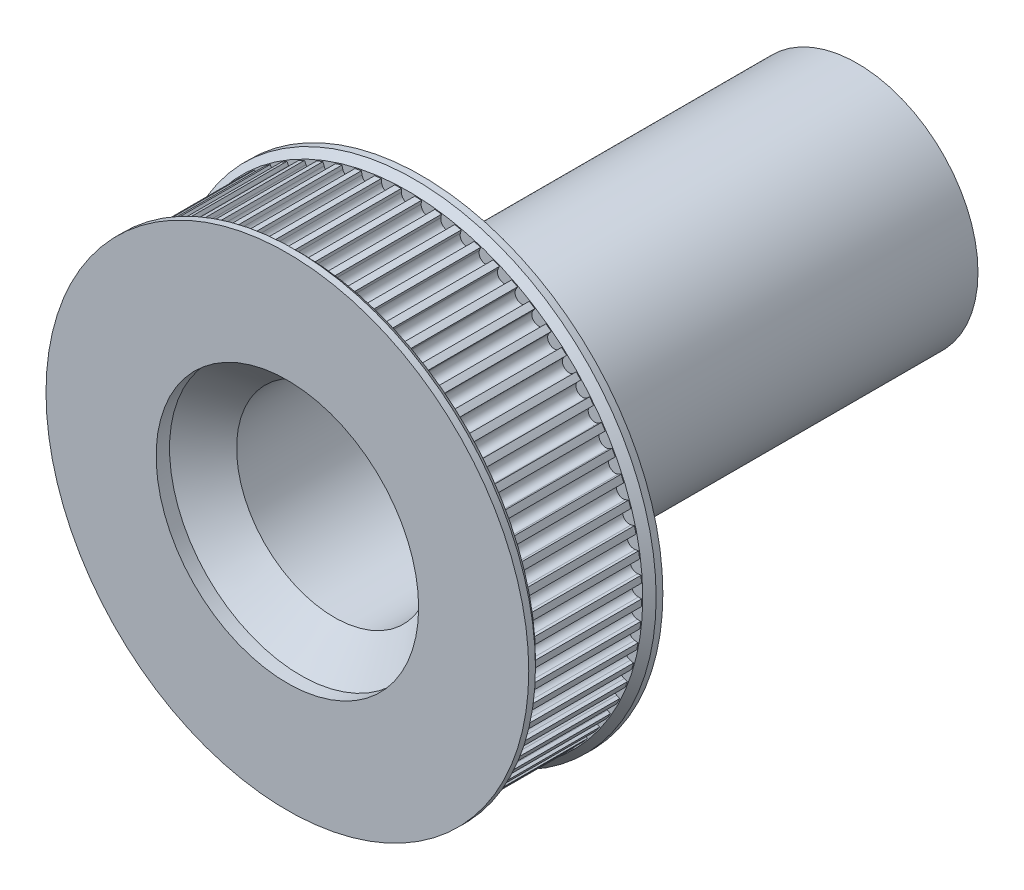
SolidWorks part; units mm, degrees
material "PA Type 6"
ref_plane "Front Plane" through (0, 0, 0) normal (0, 0, 1) x (1, 0, 0)
ref_plane "Top Plane" through (0, 0, 0) normal (0, 1, 0) x (1, 0, 0)
ref_plane "Right Plane" through (0, 0, 0) normal (1, 0, 0) x (0, 0, -1)
sketch "Sketch1" plane through (0, 0, 0) normal (0, 0, 1) x (1, 0, 0)
  circle A0 centre (0, 0) radius 18
extrude "Boss-Extrude1" add sketch "Sketch1" along normal blind 83
sketch "Sketch2" plane through (0, 0, 83) normal (0, 0, 1) x (1, 0, 0)
  circle A0 centre (0, 0) radius 14.576
extrude "Cut-Extrude1" cut sketch "Sketch2" against normal blind 70
sketch "Sketch3" plane through (0, 0, 0) normal (0, 0, -1) x (-1, 0, 0)
  circle A0 centre (0, 0) radius 4.5
  circle A1 centre (0, 0) radius 18 construction
  dimension "D1" = 9
extrude "Cut-Extrude2" cut sketch "Sketch3" against normal blind 60
sketch "Sketch4" plane through (0, 0, 83) normal (0, 0, 1) x (1, 0, 0)
  circle A0 centre (0, 0) radius 14.576
  circle A1 centre (0, 0) radius 34.85
  dimension "D1" = 69.7
extrude "Boss-Extrude2" add sketch "Sketch4" against normal blind 18
sketch "Sketch5" plane through (0, 0, 83) normal (0, 0, 1) x (1, 0, 0)
  circle A0 centre (1.619, -28.1194) radius 3.1814
extrude "Cut-Extrude3" cut sketch "Sketch5" against normal blind 4 from offset 13 offset against normal yes
chamfer "Chamfer2" distance 5 angle 45 1 edges at (14.576, 0, 13)
chamfer "Chamfer3" distance 5 angle 45 1 edges at (14.576, 0, 83)
sketch "Sketch6" plane through (0, 0, 83) normal (0, 0, 1) x (1, 0, 0)
  line L0 (0, 35.6693) -> (0, 34.3375) construction
  line L1 (1, 35.6693) -> (1, 34.3375)
  line L2 (-1, 35.6693) -> (-1, 34.3375)
  arc A0 (1, 35.6693) -> (-1, 35.6693) centre (0, 35.6693) ccw
  arc A1 (-1, 34.3375) -> (1, 34.3375) centre (0, 34.3375) ccw
  point P2 (0, 35.0034)
  dimension "D1" = 1
extrude "Cut-Extrude4" cut sketch "Sketch6" against normal blind 18
pattern_circular "CirPattern1" count 73 over 360 about axis through (0, 0, 83) along (0, 0, 1) of "Cut-Extrude4"
sketch "Sketch7" plane through (0, 0, 83) normal (0, 0, 1) x (1, 0, 0)
  circle A0 centre (0, 0) radius 19.576
  circle A1 centre (0, 0) radius 36
extrude "Boss-Extrude3" add sketch "Sketch7" along normal blind 2
pattern_linear "LPattern1" count 2 spacing 18 along (0, 0, -1) of "Boss-Extrude3"
chamfer "Chamfer4" distance 1 angle 45 2 edges at (36, 0, 83) (36, 0, 67)
sketch "Эскиз2" plane through (0, 0, 0) normal (0, 0, -1) x (-1, 0, 0)
  line L1 (-2, 8.5265) -> (2, 8.5265)
  line L2 (-2, 8.5265) -> (-2, 0.0452)
  line L3 (-2, 0.0452) -> (2, 0.0452)
  line L4 (2, 8.5265) -> (2, 0.0452)
  line L5 (-2, 8.5265) -> (2, 0.0452) construction
  line L6 (-2, 0.0452) -> (2, 8.5265) construction
  point P0 (0, 4.2859)
  dimension "D1" = 4
extrude "Вырез-Вытянуть2" cut sketch "Эскиз2" against normal blind 12
sketch "Sketch8" plane through (0, 0, 65) normal (0, 0, -1) x (-1, 0, 0)
  circle A0 centre (0, 0) radius 20.3402
  circle A1 centre (0, 0) radius 36 construction
  circle A2 centre (0, 0) radius 32
extrude "Cut-Extrude5" cut sketch "Sketch8" against normal blind 2
chamfer "Chamfer5" distance 2 angle 45 1 edges at (-32, 0, 65)
chamfer "Chamfer6" distance 2 angle 45 1 edges at (18, 0, 65)
